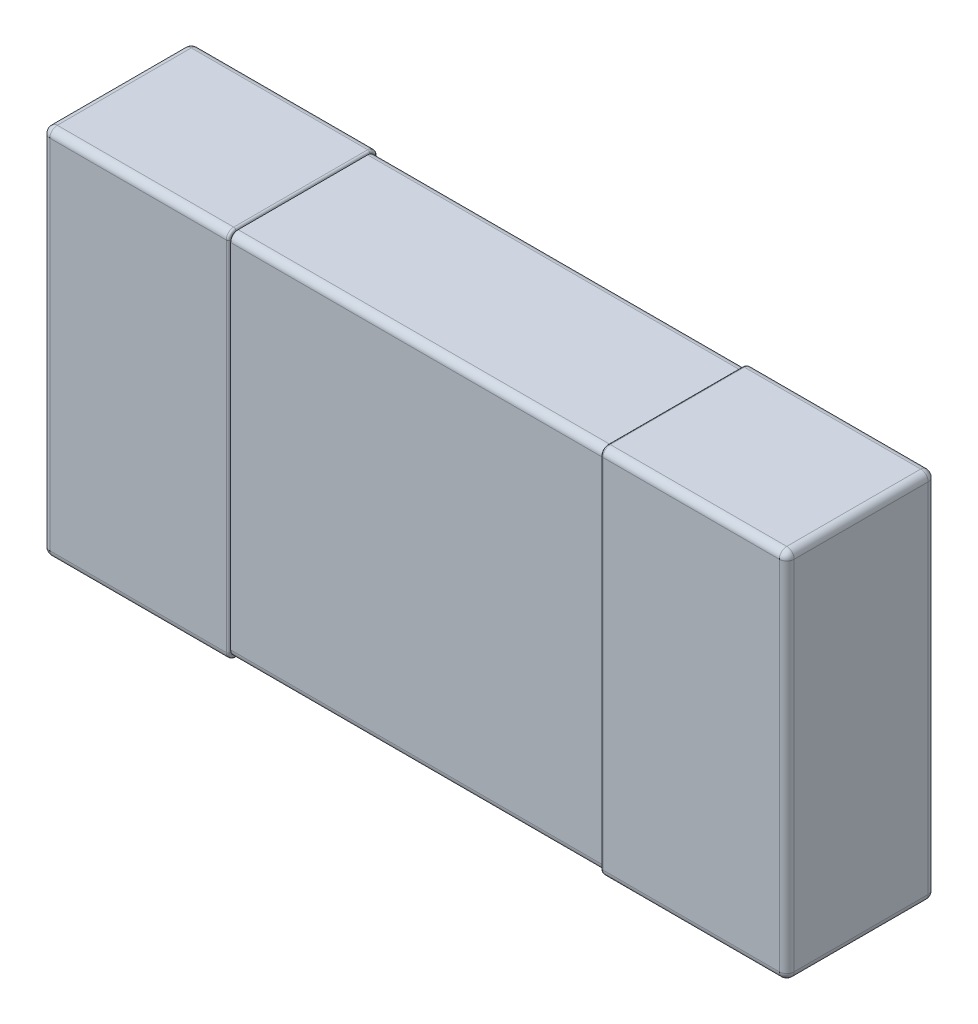
SolidWorks part; units mm, degrees
ref_plane "Top Plane" through (0, 0, 0) normal (0, 0, 1) x (1, 0, 0)
ref_plane "Front Plane" through (0, 0, 0) normal (0, 1, 0) x (1, 0, 0)
ref_plane "Side Plane" through (0, 0, 0) normal (1, 0, 0) x (0, 0, -1)
sketch "Sketch1" plane through (0, 0, 0) normal (0, 0, 1) x (1, 0, 0)
  line L1 (-0.5, 0.25) -> (0.5, 0.25)
  line L2 (-0.5, 0.25) -> (-0.5, -0.25)
  line L3 (-0.5, -0.25) -> (0.5, -0.25)
  line L4 (0.5, 0.25) -> (0.5, -0.25)
  dimension "D1" = 1
  dimension "D2" = 0.5
  dimension "D3" = 0.5
  dimension "D4" = 0.25
extrude "All body" add sketch "Sketch1" along normal blind 0.2
sketch "Sketch2" plane through (0, 0, 0) normal (1, 0, 0) x (0, 0, -1)
  line L14 (-0.003, 0.247) -> (-0.197, 0.247)
  line L15 (-0.003, -0.247) -> (-0.003, 0.247)
  line L16 (-0.197, -0.247) -> (-0.003, -0.247)
  line L17 (-0.197, 0.247) -> (-0.197, -0.247)
  line L18 (-0.003, 0.247) -> (-0.197, 0.247)
  line L19 (-0.003, -0.247) -> (-0.003, 0.247)
  line L20 (-0.197, -0.247) -> (-0.003, -0.247)
  line L21 (-0.197, 0.247) -> (-0.197, -0.247)
  dimension "D1" = 0.003
extrude "Cut out the body for pin" cut sketch "Sketch2" against normal blind 0.25 and the other way blind 0.25 flip side to cut
fillet "Body fillet" radius 0.01 4 edges at (0, 0.247, 0.003) (0, 0.247, 0.197) (0, -0.247, 0.003) (0, -0.247, 0.197)
fillet "Pin fillet a" radius 0.01 16 edges at (0.5, -0.25, 0.1) (0.5, 0, 0.2) (0.5, 0.25, 0.1) (0.5, 0, 0) (-0.5, 0.25, 0.1) (-0.5, 0, 0.2) (-0.5, -0.25, 0.1) (-0.5, 0, 0) (0.375, 0.25, 0.2) (0.375, -0.25, 0.2) (0.375, -0.25, 0) (0.375, 0.25, 0) (-0.375, 0.25, 0) (-0.375, -0.25, 0) (-0.375, 0.25, 0.2) (-0.375, -0.25, 0.2)
fillet "Pin fillet b" radius 0.003 16 edges at (0.25, -0.2471, 0.1971) (0.25, -0.25, 0.1) (0.25, -0.2471, 0.0029) (0.25, 0, 0) (0.25, 0.2471, 0.0029) (0.25, 0.25, 0.1) (0.25, 0.2471, 0.1971) (-0.25, -0.2471, 0.1971) (-0.25, -0.25, 0.1) (-0.25, -0.2471, 0.0029) (-0.25, 0, 0) (-0.25, 0.2471, 0.0029) (-0.25, 0.25, 0.1) (-0.25, 0.2471, 0.1971) (0.25, 0, 0.2) (-0.25, 0, 0.2)
